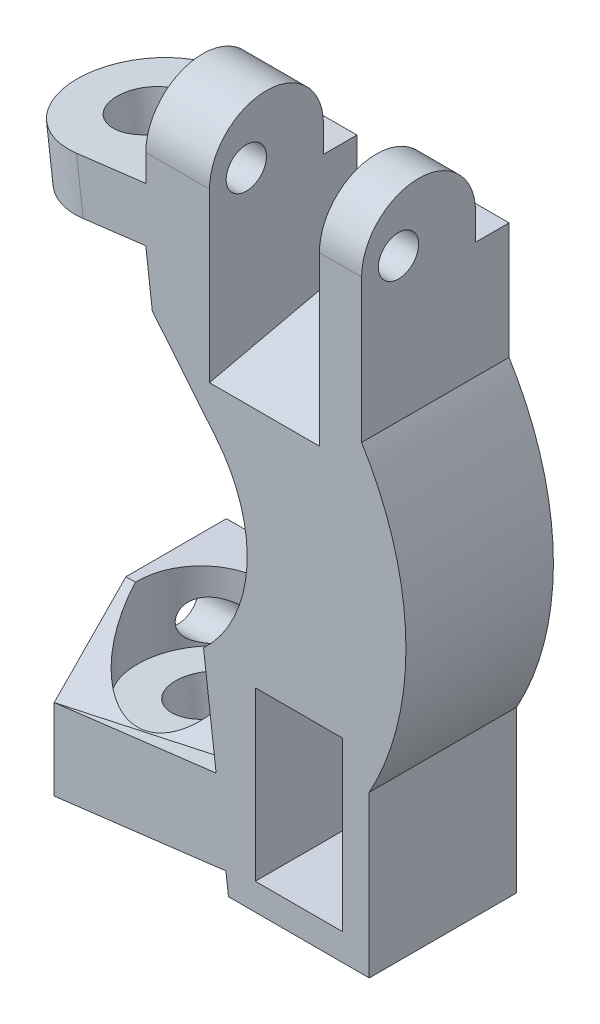
SolidWorks part; units mm, degrees
ref_plane "Front Plane" through (0, 0, 0) normal (0, 0, 1) x (1, 0, 0)
ref_plane "Top Plane" through (0, 0, 0) normal (0, 1, 0) x (1, 0, 0)
ref_plane "Right Plane" through (0, 0, 0) normal (1, 0, 0) x (0, 0, -1)
sketch "Sketch1" plane through (0, 0, 0) normal (0, 0, 1) x (1, 0, 0)
  line L0 (0, 0) -> (-10.5, 0)
  line L1 (-23.5, 0) -> (-10.6931, 1.5725)
  line L2 (0, 0) -> (0, 12)
  line L3 (-0.5696, 34.3109) -> (-0.5696, 43)
  line L4 (-0.5696, 43) -> (-16.6696, 43)
  line L5 (-16.6696, 38.97) -> (-16.1821, 34.9998)
  line L6 (-16.1821, 34.9998) -> (-11.433, 29.1949)
  line L7 (-5.25, 0) -> (-5.25, 18.4215) construction
  line L8 (-8.5, 14.5) -> (-2, 14.5)
  line L9 (-8.5, 14.5) -> (-8.5, 2)
  line L10 (-8.5, 2) -> (-2, 2)
  line L11 (-2, 14.5) -> (-2, 2)
  line L12 (-10.5, 0) -> (-10.6931, 1.5725)
  line L13 (-23.5, 6.0451) -> (-11.4243, 7.5278)
  line L14 (-23.5, 6.0451) -> (-23.5, 0)
  line L15 (-17.4621, 6.7864) -> (-21.8308, 42.3663) construction
  line L16 (-16.6696, 38.97) -> (-21.3433, 38.3961)
  line L17 (-21.3433, 38.3961) -> (-21.8308, 42.3663)
  line L18 (-21.8308, 42.3663) -> (-16.6696, 43)
  line L19 (-11.4243, 7.5278) -> (-12.3599, 15.1476)
  arc A0 (-12.3599, 15.1476) -> (-11.433, 29.1949) centre (-19.4121, 22.6672) ccw
  arc A1 (0, 12) -> (-0.5696, 34.3109) centre (-19.4121, 22.6672) ccw
  point P17 (-5.25, 2)
  point P23 (-19.4121, 22.6672)
  dimension "D3" = 10.5
  dimension "D6" = 97
  dimension "D1" = 16.1
  dimension "D2" = 43
  dimension "D4" = 6.5
  dimension "D5" = 12.5
  dimension "D7" = 7
  dimension "D8" = 16
  dimension "D9" = 15
  dimension "D10" = 6
  dimension "D11" = 2
  dimension "D12" = 5.2
  dimension "D13" = 4
  dimension "D14" = 4
  dimension "D15" = 12
  dimension "D16" = 7.5
extrude "Main Base" add sketch "Sketch1" along normal blind 11
sketch "Sketch2" plane through (-0.5696, 0, 0) normal (1, 0, 0) x (0, 0, -1)
  line L0 (-11, 43) -> (-11, 45)
  line L1 (-2.5, 43) -> (-2.5, 45)
  line L2 (-11, 0) -> (0, 0) construction
  line L5 (-11, 43) -> (-2.5, 43)
  arc A0 (-2.5, 45) -> (-11, 45) centre (-6.75, 45) ccw
  point P5 (0, 0)
  point P7 (0, 0)
  point P10 (-2.5077, 43)
  dimension "D2" = 8.5
  dimension "D1" = 45
extrude "Top Link Holes" add sketch "Sketch2" against normal up to vertex (16.1 mm away) up to point (-16.6696, 43, 11)
sketch "Sketch3" plane through (-5.4489, 44.3777, 0) normal (-0.1219, 0.9925, 0) x (0.9925, 0.1219, 0)
  line L0 (-16.5049, -11) -> (-16.5049, 0) construction
  line L1 (-11.3049, 0) -> (-16.5049, 0) construction
  line L2 (-16.5049, 0) -> (-16.5049, -11)
  arc A0 (-16.5049, 0) -> (-16.5049, -11) centre (-16.5049, -5.5) ccw
extrude "Steering Mount Boss" add sketch "Sketch3" against normal up to surface (4 mm away) up to face at (-19.0064, 38.683, 5.5)
ref_plane "Plane2" through (-7.8196, 0, 0) normal (1, 0, 0) x (0, 0, -1)
sketch "Sketch5" plane through (-7.8196, 0, 0) normal (1, 0, 0) x (0, 0, -1)
  line L0 (-11, 32.5) -> (0, 35)
  line L1 (-11, 34.3109) -> (-11, 45) construction
  line L2 (0, 34.3109) -> (0, 43) construction
  line L3 (0, 43) -> (-2.5, 43)
  line L4 (-2.5, 43) -> (-2.5, 45)
  line L5 (0, 35) -> (0, 43)
  line L8 (-11, 32.5) -> (-11, 45)
  line L9 (-11, 0) -> (0, 0) construction
  arc A0 (-2.5, 45) -> (-11, 45) centre (-6.75, 45) ccw
  dimension "D1" = 35
  dimension "D2" = 32.5
extrude "Cut for Link" cut sketch "Sketch5" against normal mid plane 8.2
sketch "Sketch12" plane through (-23.5, 0, 0) normal (-1, 0, 0) x (0, 0, 1)
  line L0 (11, 0) -> (0, 0) construction
  line L1 (11, 6.0451) -> (11, 0) construction
  line L2 (11, 6.0451) -> (0, 6.0451) construction
  line L3 (0, 6.0451) -> (0, 0) construction
  line L4 (11, 6.0451) -> (0, 6.0451)
  line L5 (0, 6.0451) -> (0, 4.854)
  line L6 (3.3042, 4.4) -> (15.7082, 4.4) construction
  line L7 (5.65, 11.5) -> (-1.85, 11.5)
  line L9 (5.65, 11.5) -> (11, 6.0451)
  line L10 (-1.85, 8) -> (-1.85, 11.5)
  arc A1 (-1.85, 8) -> (0, 4.854) centre (1.75, 8) ccw
  point P21 (-1.3532, 6.1752)
  dimension "D5" = 3.6
  dimension "D1" = 8
  dimension "D2" = 9.25
  dimension "D3" = 11.5
  dimension "D4" = 7.5
extrude "Boss-Extrude6" add sketch "Sketch12" against normal up to surface (11.588 mm away) up to face at (-11.8921, 11.3377, 5.5)
sketch "Sketch4" plane through (-5.4489, 44.3777, 0) normal (-0.1219, 0.9925, 0) x (0.9925, 0.1219, 0)
  circle A0 centre (-16.5049, -5.5) radius 2.5
  arc A1 (-16.5049, 0) -> (-16.5049, -11) centre (-16.5049, -5.5) ccw construction
  dimension "D1" = 5
extrude "Steering mount holes" cut sketch "Sketch4" against normal up to surface (41.8471 mm away) up to face at (-17.0965, 0.7862, 5.5)
ref_axis "Axis1" through (-15.1784, -11.8133, 5.5) along (-0.1219, 0.9925, 0)
sketch "Sketch13" plane through (-23.5, 0, 0) normal (-1, 0, 0) x (0, 0, 1)
  circle A0 centre (1.75, 8) radius 1.5
  arc A1 (-1.85, 8) -> (0, 4.854) centre (1.75, 8) ccw construction
  dimension "D1" = 3
extrude "Cut-Extrude8" cut sketch "Sketch13" against normal up to surface (15 mm away) up to face at (-8.5, 8.25, 5.5)
sketch "Sketch14" plane through (0, 11.5, 0) normal (0, 1, 0) x (1, 0, 0)
  circle A0 centre (-18.0409, -5.5) radius 4.75
  ellipse E1 centre (-18.0409, -5.5) end of major axis (-20.5597, -5.5) minor radius 2.5 (-15.5267, -5.65) -> (-20.5551, -5.65) ccw construction
  dimension "D1" = 9.5
extrude "Cut-Extrude9" cut sketch "Sketch14" against normal up to surface (4.7846 mm away) up to face at (-15.4495, 7.0335, 10.5153)
sketch "Sketch15" plane through (-0.5696, 0, 0) normal (1, 0, 0) x (0, 0, -1)
  line L0 (-11, 34.3109) -> (0, 34.3109) construction
  circle A0 centre (-8.25, 45) radius 1.5
  arc A1 (-2.5, 45) -> (-11, 45) centre (-6.75, 45) ccw construction
  point P4 (-8.0473, 45)
  point P8 (-6.75, 49.25)
  dimension "D1" = 3
  dimension "D2" = 10.6891
  dimension "D3" = 1.5
extrude "Cut-Extrude10" cut sketch "Sketch15" against normal up to surface (16.1 mm away) up to face at (-16.6696, 45.0625, 6.75)
